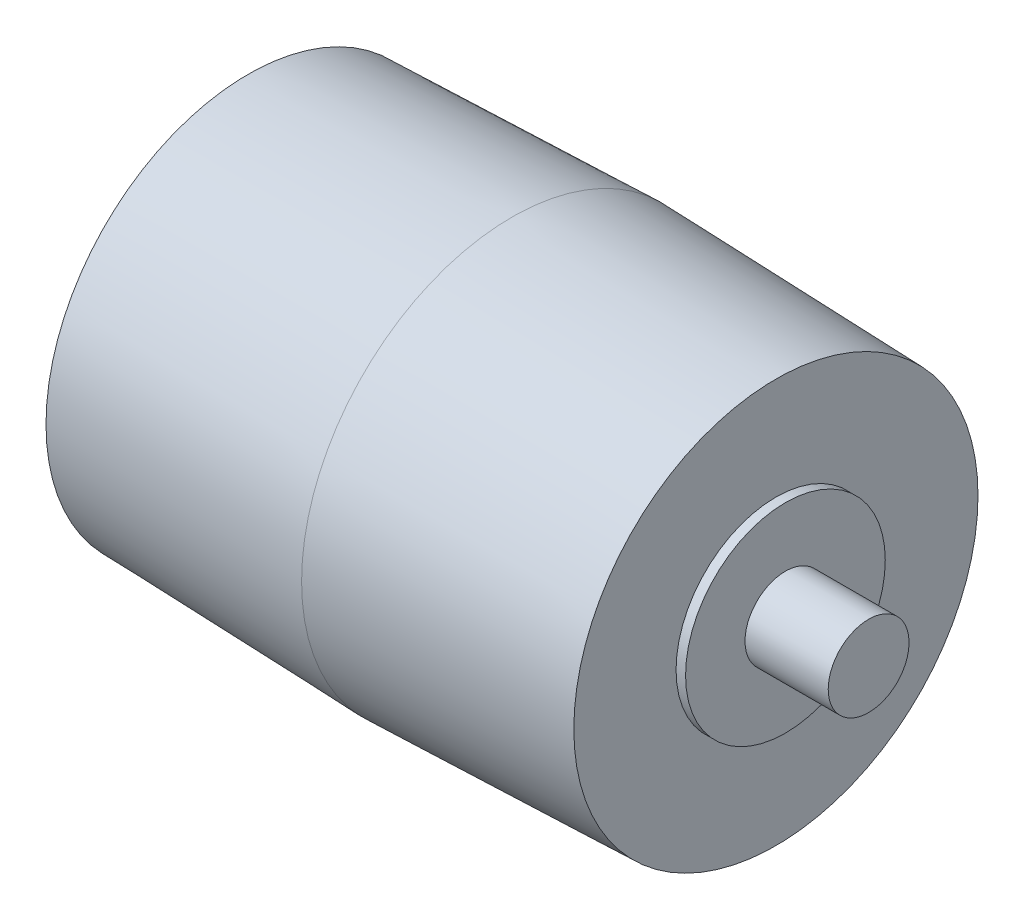
SolidWorks part; units mm, degrees
ref_plane "Front Plane" through (0, 0, 0) normal (0, 0, 1) x (1, 0, 0)
ref_plane "Top Plane" through (0, 0, 0) normal (0, 1, 0) x (1, 0, 0)
ref_plane "Right Plane" through (0, 0, 0) normal (1, 0, 0) x (0, 0, -1)
sketch "Sketch1" plane through (0, 0, 0) normal (0, 0, 1) x (1, 0, 0)
  line L0 (-9.525, 0) -> (-9.525, 1.0795)
  line L1 (-9.525, 1.0795) -> (-7.3025, 1.0795)
  line L2 (-7.3025, 1.0795) -> (-7.3025, 2.667)
  line L3 (-7.3025, 2.667) -> (-7.0485, 2.667)
  line L4 (-7.0485, 2.667) -> (-7.0485, 5.3975)
  line L5 (-7.0485, 5.3975) -> (0, 5.6197)
  line L6 (0, 5.6197) -> (0, 0) construction
  line L7 (9.525, 0) -> (-9.525, 0) construction
  line L8 (7.0485, 5.3975) -> (0, 5.6197)
  line L9 (7.0485, 2.667) -> (7.0485, 5.3975)
  line L10 (7.3025, 2.667) -> (7.0485, 2.667)
  line L11 (7.3025, 1.0795) -> (7.3025, 2.667)
  line L12 (9.525, 1.0795) -> (7.3025, 1.0795)
  line L13 (9.525, 0) -> (9.525, 1.0795)
  line L14 (-9.525, 0) -> (9.525, 0)
  dimension "D1" = 19.05
  dimension "D2" = 2.159
  dimension "D3" = 14.605
  dimension "D4" = 14.097
  dimension "D5" = 11.2395
  dimension "D6" = 10.795
  dimension "D7" = 5.334
revolve "Revolve1" add sketch "Sketch1" angle 360 about L14
